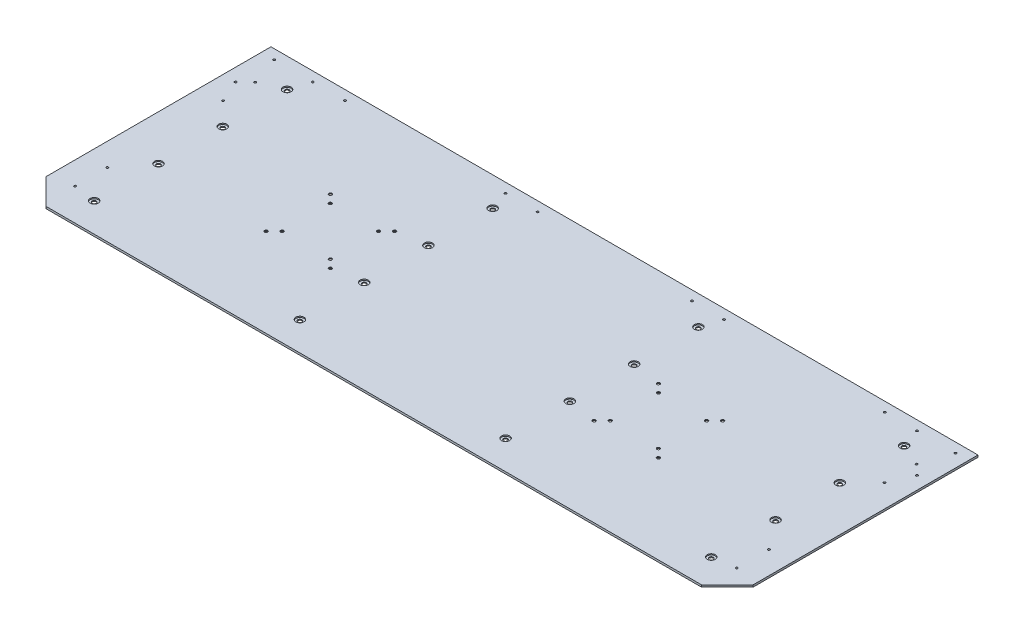
SolidWorks part; units mm, degrees
ref_plane "Front Plane" through (0, 0, 0) normal (0, 0, 1) x (1, 0, 0)
ref_plane "Top Plane" through (0, 0, 0) normal (0, 1, 0) x (1, 0, 0)
ref_plane "Right Plane" through (0, 0, 0) normal (1, 0, 0) x (0, 0, -1)
sketch "Sketch1" plane through (0, 0, 0) normal (0, 1, 0) x (1, 0, 0)
  line L1 (-550, -195) -> (550, -195)
  line L2 (-550, -195) -> (-550, 195)
  line L3 (-550, 195) -> (550, 195)
  line L4 (550, -195) -> (550, 195)
  line L5 (-550, -195) -> (550, 195) construction
  line L6 (-550, 195) -> (550, -195) construction
  point P0 (0, 0)
  dimension "D1" = 1100
  dimension "D2" = 390
extrude "Plate" add sketch "Sketch1" along normal blind 3.175
hole_wizard "Monitor Holes" positions "Sketch6" profile "Sketch7" countersink size "M4" standard "ANSI Metric" end condition through all
sketch "Sketch6" plane through (0, 0, 0) normal (0, -1, 0) x (-1, 0, 0)
  line L9 (-292.7, -44.9) -> (-217.7, -44.9)
  line L10 (-292.7, -44.9) -> (-292.7, 30.1)
  line L11 (-292.7, 30.1) -> (-217.7, 30.1)
  line L12 (-217.7, -44.9) -> (-217.7, 30.1)
  line L13 (-292.7, -44.9) -> (-217.7, 30.1) construction
  line L14 (-292.7, 30.1) -> (-217.7, -44.9) construction
  line L16 (-305.2, -57.4) -> (-205.2, -57.4)
  line L17 (-305.2, -57.4) -> (-305.2, 42.6)
  line L18 (-305.2, 42.6) -> (-205.2, 42.6)
  line L19 (-205.2, -57.4) -> (-205.2, 42.6)
  line L20 (-305.2, -57.4) -> (-205.2, 42.6) construction
  line L21 (-305.2, 42.6) -> (-205.2, -57.4) construction
  line L22 (0, 1.7463) -> (0, -1.7463) construction
  line L23 (292.7, 30.1) -> (217.7, 30.1)
  line L24 (292.7, -44.9) -> (217.7, -44.9)
  line L25 (292.7, -44.9) -> (292.7, 30.1)
  line L26 (305.2, -57.4) -> (205.2, -57.4)
  line L27 (305.2, -57.4) -> (305.2, 42.6)
  line L28 (217.7, -44.9) -> (217.7, 30.1)
  line L29 (205.2, -57.4) -> (205.2, 42.6)
  line L30 (305.2, 42.6) -> (205.2, 42.6)
  line L32 (-509.2, -159.8) -> (-1.2, -159.8)
  line L33 (-509.2, -159.8) -> (-509.2, 145)
  line L34 (-509.2, 145) -> (-1.2, 145)
  line L35 (-1.2, -159.8) -> (-1.2, 145)
  line L36 (-509.2, -159.8) -> (-1.2, 145) construction
  line L37 (-509.2, 145) -> (-1.2, -159.8) construction
  line L38 (-550, 175) -> (550, 175)
  line L39 (-550, -195) -> (-550, 195) construction
  line L40 (550, 195) -> (550, -195) construction
  line L42 (-550, 195) -> (550, 195) construction
  line L43 (0, 175) -> (0, -195)
  line L44 (550, -195) -> (-550, -195) construction
  point P80 (-217.7, 30.1)
  point P157 (-292.7, -44.9)
  point P158 (-292.7, 30.1)
  point P159 (-217.7, -44.9)
  point P161 (-205.2, 42.6)
  point P180 (-305.2, -57.4)
  point P181 (-305.2, 42.6)
  point P182 (-205.2, -57.4)
  point P186 (292.7, 30.1)
  point P187 (217.7, 30.1)
  point P188 (292.7, -44.9)
  point P189 (217.7, -44.9)
  point P190 (305.2, -57.4)
  point P191 (205.2, -57.4)
  point P192 (305.2, 42.6)
  point P193 (205.2, 42.6)
  point P307 (-255.2, -7.4)
  point P310 (-255.2, -7.4)
  point P311 (-255.2, -7.4)
  dimension "D1" = 508
  dimension "D2" = 304.8
  dimension "D3" = 20
  dimension "D4" = 75
  dimension "D5" = 100
  dimension "D6" = 40.8
  dimension "D7" = 30
sketch "Sketch7" plane through (217.7, 0, -30.1) normal (1, 0, 0) x (0, 0, -1)
  line L0 (0, 0) -> (0, 3.175)
  line L1 (0, 3.175) -> (2.4, 3.175)
  line L2 (2.4, 3.175) -> (2.4, 2.08)
  line L3 (2.4, 2.08) -> (4.48, 0)
  line L5 (4.48, 0) -> (0, 0)
  line L6 (-2.4, 2.08) -> (-4.48, 0) construction
  line L11 (0, -6.35) -> (0, 107.95) construction
  dimension "Thru Hole Dia." = 4.8
  dimension "Thru Hole Depth" = 3.175
  dimension "Near C'Sink Dia." = 8.96
  dimension "Near C'Sink Angle" = 90
hole_wizard "Strut Holes" positions "Sketch10" profile "Sketch12" tap size "M4x0.7" standard "ANSI Metric" end condition through all
sketch "Sketch10" plane through (0, 3.175, 0) normal (0, 1, 0) x (1, 0, 0)
  line L0 (-530, 180) -> (-530, 120)
  line L3 (-550, 195) -> (-550, -195) construction
  line L4 (0, -1.7463) -> (0, 1.7463) construction
  line L5 (530, 180) -> (530, 120)
  line L6 (550, 195) -> (-550, 195) construction
  point P1 (-530, 180)
  point P2 (-530, 120)
  point P11 (530, 180)
  point P12 (530, 120)
  point P13 (-530, 150)
  dimension "D1" = 60
  dimension "D2" = 45
  dimension "D3" = 20
sketch "Sketch12" plane through (-530, 3.175, -180) normal (1, 0, 0) x (0, 0, 1)
  line L0 (0, 0) -> (0, 3.175)
  line L1 (0, 3.175) -> (1.65, 3.175)
  line L2 (1.65, 3.175) -> (1.65, 0)
  line L5 (1.65, 0) -> (0, 0)
  line L11 (0, -6.35) -> (0, 107.95) construction
  dimension "Thru Tap Drill Dia." = 3.3
  dimension "Thru Tap Drill Depth" = 3.175
cosmetic thread "Hole Thread1" parameters "D2"=4
cosmetic thread "Hole Thread2" parameters "D2"=4
cosmetic thread "Hole Thread3" parameters "D2"=4
cosmetic thread "Hole Thread4" parameters "D2"=4
hole_wizard "Glare Protector Holes" positions "Sketch15" profile "Sketch16" tap size "M4x0.7" standard "ANSI Metric" end condition through all
sketch "Sketch15" plane through (0, 3.175, 0) normal (0, 1, 0) x (1, 0, 0)
  line L0 (-514.6, 135) -> (-514.6, 85)
  line L2 (-514.6, -145) -> (-514.6, -95)
  line L6 (550, 195) -> (-550, 195) construction
  line L8 (-470, 180) -> (-420, 180)
  line L10 (-170, 180) -> (-120, 180)
  line L12 (420, 180) -> (470, 180)
  line L14 (120, 180) -> (170, 180)
  line L16 (-550, 195) -> (-550, -195) construction
  line L17 (550, -195) -> (550, 195) construction
  line L18 (0, -1.7463) -> (0, 1.7463) construction
  line L19 (514.6, 135) -> (514.6, 85)
  line L21 (514.6, -145) -> (514.6, -95)
  line L22 (-550, -195) -> (550, -195) construction
  point P1 (-514.6, 135)
  point P2 (-514.6, 85)
  point P5 (-514.6, -145)
  point P6 (-514.6, -95)
  point P19 (-470, 180)
  point P20 (-420, 180)
  point P23 (-170, 180)
  point P24 (-120, 180)
  point P26 (420, 180)
  point P27 (470, 180)
  point P30 (120, 180)
  point P31 (170, 180)
  point P40 (514.6, 135)
  point P41 (514.6, 85)
  point P44 (514.6, -145)
  point P45 (514.6, -95)
  dimension "D1" = 50
  dimension "D2" = 60
  dimension "D3" = 230
  dimension "D4" = 80
  dimension "D5" = 80
  dimension "D6" = 50
  dimension "D7" = 300
  dimension "D8" = 300
  dimension "D9" = 15
  dimension "D10" = 35.4
  dimension "D11" = 45
  dimension "D12" = 50
  dimension "D13" = 44.6
sketch "Sketch16" plane through (-514.6, 3.175, -135) normal (1, 0, 0) x (0, 0, 1)
  line L0 (0, 0) -> (0, 3.175)
  line L1 (0, 3.175) -> (1.65, 3.175)
  line L2 (1.65, 3.175) -> (1.65, 0)
  line L5 (1.65, 0) -> (0, 0)
  line L11 (0, -6.35) -> (0, 107.95) construction
  dimension "Thru Tap Drill Dia." = 3.3
  dimension "Thru Tap Drill Depth" = 3.175
cosmetic thread "Hole Thread5" parameters "D2"=4
cosmetic thread "Hole Thread6" parameters "D2"=4
cosmetic thread "Hole Thread9" parameters "D2"=4
cosmetic thread "Hole Thread10" parameters "D2"=4
cosmetic thread "Hole Thread11" parameters "D2"=4
cosmetic thread "Hole Thread12" parameters "D2"=4
cosmetic thread "Hole Thread13" parameters "D2"=4
cosmetic thread "Hole Thread14" parameters "D2"=4
cosmetic thread "Hole Thread15" parameters "D2"=4
cosmetic thread "Hole Thread16" parameters "D2"=4
cosmetic thread "Hole Thread17" parameters "D2"=4
cosmetic thread "Hole Thread18" parameters "D2"=4
cosmetic thread "Hole Thread21" parameters "D2"=4
cosmetic thread "Hole Thread22" parameters "D2"=4
cosmetic thread "Hole Thread23" parameters "D2"=4
cosmetic thread "Hole Thread24" parameters "D2"=4
chamfer "Chamfer1" distance 40 angle 45 2 edges at (550, 1.5875, 195) (-550, 1.5875, 195)
hole_wizard "Carriage Holes" positions "Sketch21" profile "Sketch23" counterbore size "M5" standard "ANSI Metric" end condition through all
sketch "Sketch21" plane through (0, 3.175, 0) normal (0, 1, 0) x (1, 0, 0)
  point P0 (160, -150)
  point P2 (480, -150)
  point P14 (160, -50)
  point P15 (480, -50)
  point P16 (160, 50)
  point P17 (480, 50)
  point P18 (160, 150)
  point P19 (480, 150)
  dimension "D1" = 160
  dimension "D2" = 150
  dimension "D3" = 480
  dimension "D4" = 4
sketch "Sketch23" plane through (160, 3.175, 150) normal (1, 0, 0) x (0, 0, 1)
  line L0 (0, 0) -> (0, 3.175)
  line L1 (0, 3.175) -> (3.175, 3.175)
  line L3 (3.175, 3.175) -> (3.175, 1.7875)
  line L4 (3.175, 1.7875) -> (6.35, 1.7875)
  line L5 (6.35, 1.7875) -> (6.35, 0)
  line L7 (6.35, 0) -> (0, 0)
  line L11 (0, -6.35) -> (0, 107.95) construction
  dimension "Thru Hole Dia." = 6.35
  dimension "Thru Hole Depth" = 3.175
  dimension "C'Bore Dia." = 12.7
  dimension "C'Bore Depth" = 1.7875
mirror "Mirror1" about plane through (0, 0, 0) normal (1, 0, 0) of "Carriage Holes"
